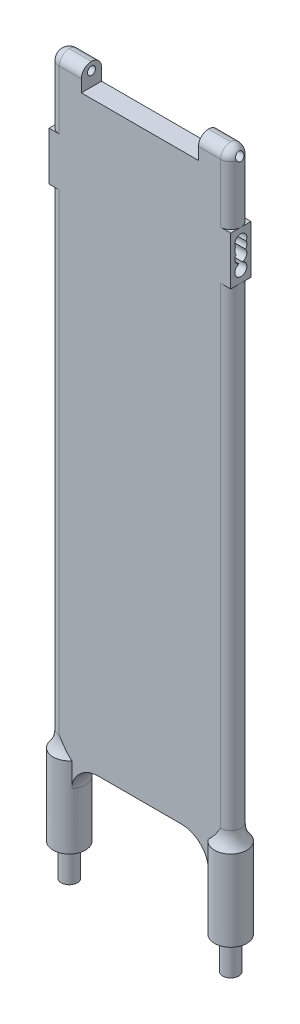
SolidWorks part; units mm, degrees
note: The reader was unsure of these and kept them because the rebuilt part matched: shared geometry of "Sketch1<3>".
ref_plane "Front Plane" through (0, 0, 0) normal (0, 0, 1) x (1, 0, 0)
ref_plane "Top Plane" through (0, 0, 0) normal (0, 1, 0) x (1, 0, 0)
ref_plane "Right Plane" through (0, 0, 0) normal (1, 0, 0) x (0, 0, -1)
sketch "Sketch1" plane through (0, 0, 0) normal (0, 1, 0) x (1, 0, 0)
  line L0 (-20, 0) -> (20, 0) construction
  circle A0 centre (-20, 0) radius 2
  circle A1 centre (20, 0) radius 2
  circle A2 centre (-20, 0) radius 4
  circle A3 centre (20, 0) radius 4
  point P8 (0, 0)
  dimension "D2" = 4
  dimension "D1" = 40
  dimension "D3" = 2
extrude "Boss-Extrude1" add sketch "Sketch1" against normal blind 8
extrude "Boss-Extrude2" add sketch "Sketch1<3>" along normal blind 20
sketch "Sketch1<3>" plane through (0, 0, 0) normal (0, 1, 0) x (1, 0, 0) same geometry as "Sketch1"
sketch "Sketch2" plane through (0, 20, 0) normal (0, 1, 0) x (1, 0, 0)
  line L0 (-20, 0) -> (20, 0) construction
  line L1 (-20, 2.5) -> (20, 2.5)
  line L2 (-20, -2.5) -> (20, -2.5)
  arc A0 (-20, 2.5) -> (-20, -2.5) centre (-20, 0) ccw
  arc A1 (20, -2.5) -> (20, 2.5) centre (20, 0) ccw
  point P4 (0, 0)
  dimension "D1" = 5
extrude "Boss-Extrude3" add sketch "Sketch2" along normal blind 150
fillet "Fillet1" radius 6 2 edges at (-16, 20, 0) (16, 20, 0)
fillet "Fillet2" radius 6 2 edges at (-22.5, 20, 0) (22.5, 20, 0)
sketch "Sketch3" plane through (0, 0, 2.5) normal (0, 0, 1) x (1, 0, 0)
  line L0 (-20, 170) -> (20, 170) construction
  line L1 (-14.5, 170) -> (14.5, 170)
  line L2 (-14.5, 170) -> (-14.5, 164.5)
  line L3 (-14.5, 164.5) -> (14.5, 164.5)
  line L4 (14.5, 170) -> (14.5, 164.5)
  dimension "D1" = 5.5
  dimension "D2" = 8
  dimension "D3" = 8
extrude "Cut-Extrude1" cut sketch "Sketch3" against normal mid plane 10
sketch "Sketch4" plane through (14.5, 0, 0) normal (-1, 0, 0) x (0, 0, 1)
  line L0 (2.5, 170) -> (-2.5, 170) construction
  circle A0 centre (0, 168) radius 1
  point P4 (0, 170)
  dimension "D1" = 2
  dimension "D2" = 2
extrude "Cut-Extrude2" cut sketch "Sketch4" against normal through all both and the other way through all
fillet "Fillet3" radius 2.5 6 edges at (17.25, 170, 2.5) (17.25, 170, -2.5) (-17.25, 170, -2.5) (-17.25, 170, 2.5) (22.5, 170, 0) (-22.5, 170, 0)
ref_plane "Plane1" through (-20, 0, 0) normal (1, 0, 0) x (0, -1, 0)
sketch "Sketch5" plane through (-20, 0, 0) normal (1, 0, 0) x (0, -1, 0)
  line L0 (-167.5, 0) -> (-23.9686, 0) construction
  circle A0 centre (-150, 0) radius 1.5
  arc A1 (-167.5, -0.866) -> (-167.5, 0.866) centre (-168, 0) ccw construction
  circle A3 centre (-148.59, 0) radius 1.5
  circle A4 centre (-146.71, 0) radius 1.5
  circle A5 centre (-143.83, 0) radius 1.5
  dimension "D1" = 3
  dimension "D2" = 18
  dimension "D5" = 19.41
  dimension "D6" = 21.29
  dimension "D7" = 24.17
extrude "Cut-Extrude3" cut sketch "Sketch5" against normal blind 3 and the other way blind 6
sketch "Sketch9" plane through (-20, 0, 0) normal (1, 0, 0) x (0, -1, 0)
  line L0 (-167.5, 2.5) -> (-23.9686, 2.5) construction
  line L1 (-140.915, 2.5) -> (-152.915, 2.5)
  line L2 (-140.915, 2.5) -> (-140.915, -2.5)
  line L3 (-140.915, -2.5) -> (-152.915, -2.5)
  line L4 (-152.915, 2.5) -> (-152.915, -2.5)
  line L5 (-167.5, -2.5) -> (-23.9686, -2.5) construction
  line L6 (-142.33, 0) -> (-151.5, 0) construction
  arc A0 (-147.65, 1.1689) -> (-149.295, 1.324) centre (-148.59, 0) ccw construction
  arc A1 (-145.27, 0.42) -> (-147.65, 1.1689) centre (-146.71, 0) ccw construction
  arc A2 (-149.295, 1.324) -> (-149.295, -1.324) centre (-150, 0) ccw construction
  arc A3 (-147.65, 1.1689) -> (-149.295, 1.324) centre (-148.59, 0) ccw
  arc A4 (-145.27, 0.42) -> (-147.65, 1.1689) centre (-146.71, 0) ccw
  arc A5 (-149.295, 1.324) -> (-149.295, -1.324) centre (-150, 0) ccw
  arc A6 (-145.27, -0.42) -> (-145.27, 0.42) centre (-143.83, 0) ccw
  arc A7 (-147.65, -1.1689) -> (-145.27, -0.42) centre (-146.71, 0) ccw
  arc A8 (-149.295, -1.324) -> (-147.65, -1.1689) centre (-148.59, 0) ccw
  arc A9 (-149.295, 1.324) -> (-149.295, -1.324) centre (-150, 0) ccw
  arc A10 (-147.65, 1.1689) -> (-149.295, 1.324) centre (-148.59, 0) ccw
  arc A11 (-145.27, 0.42) -> (-147.65, 1.1689) centre (-146.71, 0) ccw
  arc A12 (-145.27, -0.42) -> (-145.27, 0.42) centre (-143.83, 0) ccw
  arc A13 (-147.65, -1.1689) -> (-145.27, -0.42) centre (-146.71, 0) ccw
  arc A14 (-149.295, -1.324) -> (-147.65, -1.1689) centre (-148.59, 0) ccw
  arc A15 (-149.295, 1.324) -> (-149.295, -1.324) centre (-150, 0) ccw
  arc A16 (-147.65, 1.1689) -> (-149.295, 1.324) centre (-148.59, 0) ccw
  arc A17 (-145.27, 0.42) -> (-147.65, 1.1689) centre (-146.71, 0) ccw
  point P29 (-146.915, 0)
  point P30 (-146.915, 2.5)
  dimension "D2" = 12
  dimension "D1" = 0
extrude "Boss-Extrude4" add sketch "Sketch9" against normal blind 2.5 contours L1 L4 L3 L2 A14 A15 A5 A3 A4 A12 A13
mirror "Mirror1" about plane through (0, 0, 0) normal (1, 0, 0) of "Cut-Extrude3", "Boss-Extrude4"
